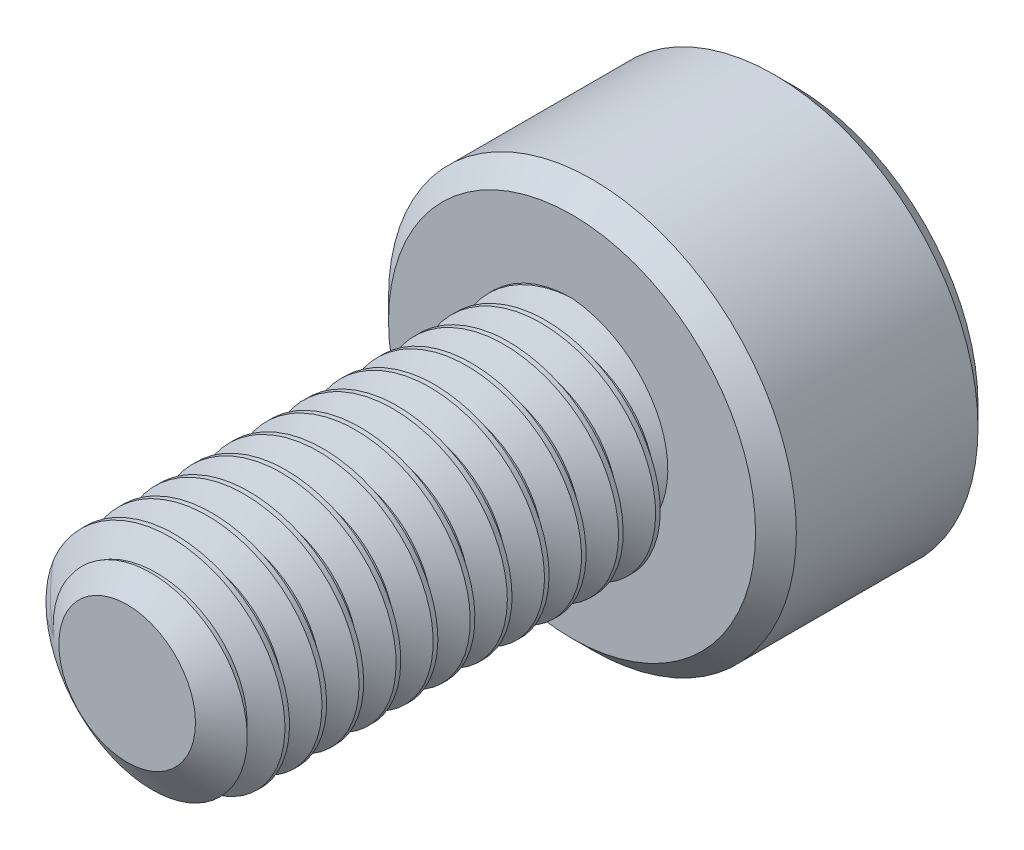
SolidWorks part; units mm, degrees
other "DetailItem1"
ref_plane "Front Plane" through (0, 0, 0) normal (0, 0, 1) x (1, 0, 0)
ref_plane "Top Plane" through (0, 0, 0) normal (0, 1, 0) x (1, 0, 0)
ref_plane "Right Plane" through (0, 0, 0) normal (1, 0, 0) x (0, 0, -1)
sketch "Sketch1" plane through (0, 0, 0) normal (0, 0, 1) x (1, 0, 0)
  circle A0 centre (0, 0) radius 1.5
  dimension "OD" = 3
extrude "Extrude1" add sketch "Sketch1" against normal blind 6
sketch "Sketch2" plane through (0, 0, 0) normal (0, 0, 1) x (1, 0, 0)
  circle A0 centre (0, 0) radius 1.5 construction
  circle A1 centre (0, 0) radius 1.5
curve "Helix/Spiral1" pitch 0.5 height 6.5 radius 1.5 centre (0, 0, 0) axis (0, 0, -1) start towards (0, 1, 0) parameters "pitch"=0.5
sketch "Sketch3" plane through (0, 0, 0) normal (1, 0, 0) x (0, 0, -1)
  line L0 (-0.4375, 1.5) -> (-0.25, 1.1752)
  line L1 (-0.25, 1.1752) -> (-0.1875, 1.1752)
  line L2 (-0.1875, 1.1752) -> (0, 1.5)
  line L3 (-0.4375, 1.5) -> (0, 1.5)
  line L4 (-0.2188, 1.5) -> (-0.2188, 1.1752) construction
  line L5 (-0.3438, 1.3376) -> (-0.0938, 1.3376) construction
  line L6 (0, 1.5) -> (0, -1.5) construction
  dimension "D1" = 0.0625
  dimension "D2" = 0.25
  dimension "D3" = 60
sweep "Cut-Sweep1" cut profiles "Sketch3" path "Helix/Spiral1"
sketch "Sketch4" plane through (0, 0, 0) normal (1, 0, 0) x (0, 0, -1)
  line L0 (0.4053, 1.5) -> (0, 0.9212)
  line L1 (0, 0.9212) -> (0, 1.5)
  line L2 (0.4053, 1.5) -> (0, 1.5)
  line L3 (-0.4375, 1.5) -> (0, 1.5) construction
  line L4 (0, 0) -> (7.0209, 0) construction
  dimension "D1" = 55
  dimension "D2" = 0.254
revolve "Cut-Revolve1" cut sketch "Sketch4" angle 360 about L4
sketch "Sketch6" plane through (0, 0, -6) normal (0, 0, -1) x (-1, 0, 0)
  circle A0 centre (0, 0) radius 2.75
  dimension "head dia" = 5.5
extrude "Extrude2" add sketch "Sketch6" along normal blind 3
sketch "Sketch7" plane through (0, 0, -9) normal (0, 0, -1) x (-1, 0, 0)
  line L1 (0, 1.4434) -> (-1.25, 0.7217)
  line L2 (-1.25, 0.7217) -> (-1.25, -0.7217)
  line L3 (-1.25, -0.7217) -> (0, -1.4434)
  line L4 (0, -1.4434) -> (1.25, -0.7217)
  line L5 (1.25, -0.7217) -> (1.25, 0.7217)
  line L6 (1.25, 0.7217) -> (0, 1.4434)
  circle A0 centre (0, 0) radius 1.25 construction
  dimension "hex dia" = 2.5
extrude "Cut-Extrude1" cut sketch "Sketch7" against normal blind 1.875
sketch "Sketch8" plane through (0, 0, -9) normal (0, 0, -1) x (-1, 0, 0)
  circle A0 centre (0, 0) radius 1.4434
extrude "Cut-Extrude2" cut sketch "Sketch8" against normal through all draft 45
chamfer "Chamfer1" distance 0.275 angle 45 2 edges at (-2.75, 0, -9) (-2.75, 0, -6)
sketch "Sketch10" plane through (0, 0, -6) normal (0, 0, 1) x (1, 0, 0)
  circle A1 centre (0, 0) radius 1.5
  circle A2 centre (0, 0) radius 1.5
  dimension "D1" = 0
ref_plane "Plane1" through (0, 0, 0) normal (0, 0, 1) x (1, 0, 0)
extrude "partial thread" [suppressed] add sketch "Sketch10" along normal up to surface (36 mm away) separate body up to plane "Plane1"
chamfer "Chamfer2" [suppressed] distance 0.06 angle 45
combine bodies "Combine1" [suppressed] operation type add bodies to combine 107 108
sketch "Sketch9" plane through (0, 0, 0) normal (1, 0, 0) x (0, 0, -1)
  line L0 (0, 1.5) -> (0, -1.5) construction
  line L1 (1.25, 1.5) -> (1.25, -1.5) construction
  dimension "D1" = 1.25
  dimension "D4" = 0.635
  dimension "D5" = 0.3302
equation "\"D3@Helix/Spiral1\" = \"screw length@Extrude1\"+\"pitch@Helix/Spiral1\""
equation "\"D1@Sketch3\" = \"pitch@Helix/Spiral1\"*.125"
equation "\"D2@Sketch3\" = \"pitch@Helix/Spiral1\"*.5"
equation "\"D1@Cut-Extrude1\" = \"hex dia@Sketch7\"*.75"
equation "\"D1@Chamfer1\" = \"head dia@Sketch6\"*.05"
equation "\"D1@Sketch9\" = \"pitch@Helix/Spiral1\"*2.5"
equation "\"D1@Chamfer2\"=\"OD@Sketch1\"*.02"
